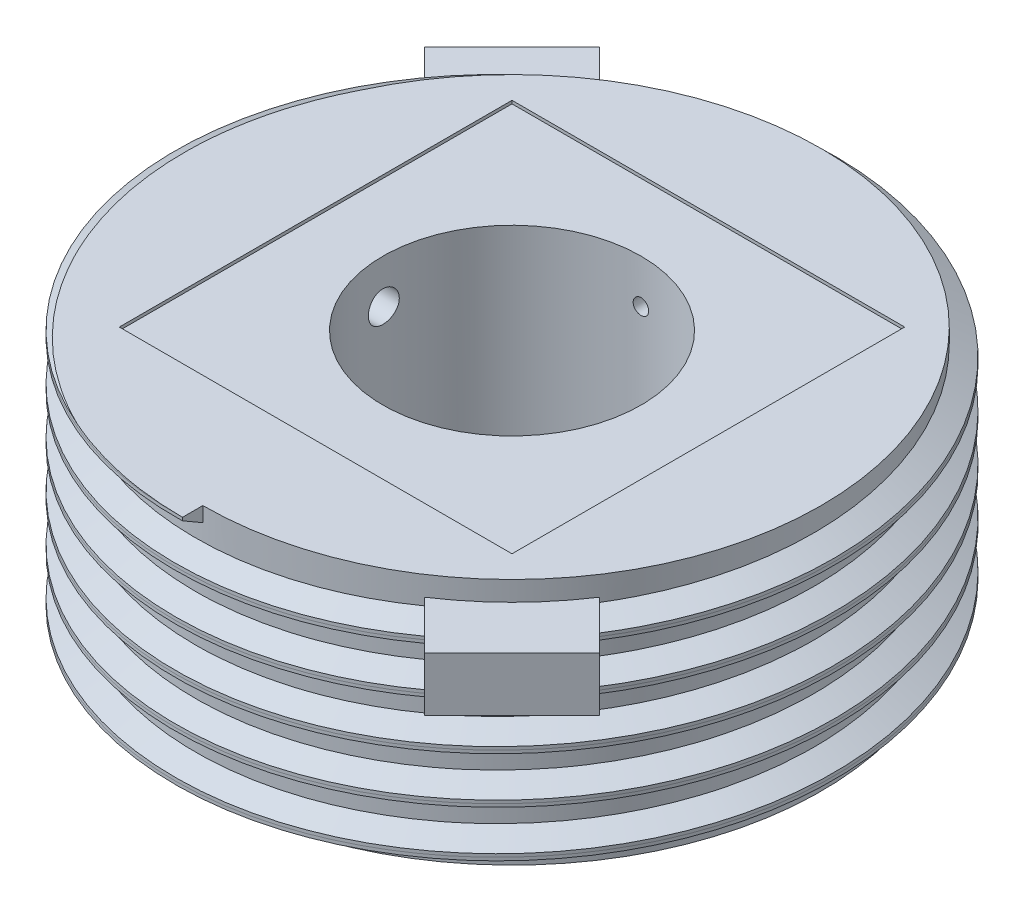
SolidWorks part; units mm, degrees
ref_plane "Front Plane" through (0, 0, 0) normal (0, 0, 1) x (1, 0, 0)
ref_plane "Top Plane" through (0, 0, 0) normal (0, 1, 0) x (1, 0, 0)
ref_plane "Right Plane" through (0, 0, 0) normal (1, 0, 0) x (0, 0, -1)
sketch "innerCircle" plane through (0, 0, 0) normal (0, 1, 0) x (1, 0, 0)
  circle A0 centre (0, 0) radius 7.35
  circle A1 centre (0, 0) radius 20
  dimension "D1" = 14.7
  dimension "D2" = 40
extrude "Circle" add sketch "innerCircle" along normal blind 16
sketch "Sketch5" plane through (0, 16, 0) normal (0, 1, 0) x (1, 0, 0)
  line L1 (12.7, 12.7) -> (-12.7, 12.7)
  line L2 (12.7, 12.7) -> (12.7, -12.7)
  line L3 (12.7, -12.7) -> (-12.7, -12.7)
  line L4 (-12.7, 12.7) -> (-12.7, -12.7)
  line L5 (12.7, 12.7) -> (-12.7, -12.7) construction
  line L6 (12.7, -12.7) -> (-12.7, 12.7) construction
  point P0 (0, 0)
  dimension "D1" = 25.4
  dimension "D2" = 25.4
sketch "Sketch11" plane through (0, 0, 0) normal (0, 0, 1) x (1, 0, 0)
  line L0 (0, 16) -> (0, 0) construction
ref_plane "Plane1" through (0, 16, 0) normal (0, 1, 0) x (1, 0, 0)
sketch "Sketch13" plane through (0, 16, 0) normal (0, 1, 0) x (1, 0, 0)
  circle A0 centre (0, 0) radius 20
curve "Helix/Spiral1" pitch 3 height 16 radius 20 centre (0, 16, 0) axis (0, -1, 0) start towards (0, 0, 1)
sketch "Sketch14" plane through (0, 0, 0) normal (1, 0, 0) x (0, 0, -1)
  line L0 (-19.8126, 16) -> (-21.3126, 16) construction
  line L1 (20, 16) -> (-20, 16) construction
  line L2 (-21.3126, 16) -> (-21.3126, 16.2)
  line L3 (-21.3126, 16.2) -> (-19.8126, 17.066)
  line L4 (-19.8126, 17.066) -> (-19.8126, 14.934)
  line L5 (-19.8126, 14.934) -> (-21.3126, 15.8)
  line L6 (-21.3126, 15.8) -> (-21.3126, 16)
  dimension "D1" = 1.5
  dimension "D2" = 60
  dimension "D3" = 0.2
sweep "Sweep1" add profiles "Sketch14" path "Helix/Spiral1"
sketch "Sketch15" plane through (0, 0, 0) normal (1, 0, 0) x (0, 0, -1)
  line L0 (0, 16) -> (0, 0) construction
  circle A0 centre (0, 12.9718) radius 1
  dimension "D1" = 2
sketch "Sketch16" plane through (0, 0, 0) normal (0, 0, 1) x (1, 0, 0)
  line L0 (0, 11.9718) -> (0, 13.9718) construction
  circle A0 centre (0, 12.9718) radius 0.5
  dimension "D1" = 1
extrude "Cut-Extrude2" cut sketch "Sketch16" against normal through all
extrude "Cut-Extrude3" cut sketch "Sketch15" against normal through all
ref_plane "Plane2" through (0, 0, 0) normal (0.7071, 0, 0.7071) x (0, -1, 0)
sketch "Sketch17" plane through (0, 0, 0) normal (0.7071, 0, 0.7071) x (0, -1, 0)
  line L1 (-11.2218, -4) -> (-14.7218, -4)
  line L2 (-11.2218, -4) -> (-11.2218, 4)
  line L3 (-11.2218, 4) -> (-14.7218, 4)
  line L4 (-14.7218, -4) -> (-14.7218, 4)
  line L5 (-11.2218, -4) -> (-14.7218, 4) construction
  line L6 (-11.2218, 4) -> (-14.7218, -4) construction
  point P0 (-12.9718, 0)
  dimension "D1" = 8
  dimension "D2" = 3.5
extrude "Boss-Extrude1" add sketch "Sketch17" along normal blind 24 and the other way blind 24
sketch "Sketch18" plane through (0, 0, 0) normal (0, 1, 0) x (1, 0, 0)
  circle A0 centre (0, 0) radius 8.35
  dimension "D1" = 16.7
extrude "Cut-Extrude4" cut sketch "Sketch18" along normal through all
sketch "Sketch19" plane through (0, 0, 0) normal (1, 0, 0) x (0, 0, -1)
  line L0 (25, -2) -> (-25, -2) construction
  line L1 (-19.9189, 0) -> (20.6045, 0)
  line L2 (-19.9189, 0) -> (-19.9189, -2)
  line L3 (-19.9189, -2) -> (20.6045, -2)
  line L4 (20.6045, 0) -> (20.6045, -2)
  spline S0 degree 2 poles (-16.6848, 12.3216) (-20, 12.1809) (-20, 12.0422) (-20, 11.8922) (-16.1803, 11.7422) (-12.3607, 11.5922) (-6.1803, 11.4422) (0, 11.2922) (6.1803, 11.1422) (12.3607, 10.9922) (16.1803, 10.8422) (20, 10.6922) (20, 10.5422) (20, 10.3922) (16.1803, 10.2422) (12.3607, 10.0922) (6.1803, 9.9422) (0, 9.7922) (-6.1803, 9.6422) (-12.3607, 9.4922) (-16.1803, 9.3422) (-20, 9.1922) (-20, 9.0422) (-20, 8.8922) (-16.1803, 8.7422) (-12.3607, 8.5922) (-6.1803, 8.4422) (0, 8.2922) (6.1803, 8.1422) (12.3607, 7.9922) (16.1803, 7.8422) (20, 7.6922) (20, 7.5422) (20, 7.3922) (16.1803, 7.2422) (12.3607, 7.0922) (6.1803, 6.9422) (0, 6.7922) (-6.1803, 6.6422) (-12.3607, 6.4922) (-16.1803, 6.3422) (-20, 6.1922) (-20, 6.0422) (-20, 5.8922) (-16.1803, 5.7422) (-12.3607, 5.5922) (-6.1803, 5.4422) (0, 5.2922) (6.1803, 5.1422) (12.3607, 4.9922) (16.1803, 4.8422) (20, 4.6922) (20, 4.5422) (20, 4.3922) (16.1803, 4.2422) (12.3607, 4.0922) (6.1803, 3.9422) (0, 3.7922) (-6.1803, 3.6422) (-12.3607, 3.4922) (-16.1803, 3.3422) (-20, 3.1922) (-20, 3.0422) (-20, 2.8922) (-16.1803, 2.7422) (-12.3607, 2.5922) (-6.1803, 2.4422) (0, 2.2922) (6.1803, 2.1422) (12.3607, 1.9922) (16.1803, 1.8422) (20, 1.6922) (20, 1.5422) (20, 1.3922) (16.1803, 1.2422) (12.3607, 1.0922) (6.1803, 0.9422) (0, 0.7922) (-6.1803, 0.6422) (-12.3607, 0.4922) (-16.1803, 0.3422) (-20, 0.1922) (-20, 0.0422) (-20, 0.0213) (-19.9189, 0) knots 0.15119 0.15119 0.15119 0.166667 0.166667 0.183333 0.183333 0.2 0.2 0.216667 0.216667 0.233333 0.233333 0.25 0.25 0.266667 0.266667 0.283333 0.283333 0.3 0.3 0.316667 0.316667 0.333333 0.333333 0.35 0.35 0.366667 0.366667 0.383333 0.383333 0.4 0.4 0.416667 0.416667 0.433333 0.433333 0.45 0.45 0.466667 0.466667 0.483333 0.483333 0.5 0.5 0.516667 0.516667 0.533333 0.533333 0.55 0.55 0.566667 0.566667 0.583333 0.583333 0.6 0.6 0.616667 0.616667 0.633333 0.633333 0.65 0.65 0.666667 0.666667 0.683333 0.683333 0.7 0.7 0.716667 0.716667 0.733333 0.733333 0.75 0.75 0.766667 0.766667 0.783333 0.783333 0.8 0.8 0.816667 0.816667 0.833333 0.833333 0.835748 0.835748 0.835748 weights 0.993509 0.954551 1 0.951057 1 0.951057 1 0.951057 1 0.951057 1 0.951057 1 0.951057 1 0.951057 1 0.951057 1 0.951057 1 0.951057 1 0.951057 1 0.951057 1 0.951057 1 0.951057 1 0.951057 1 0.951057 1 0.951057 1 0.951057 1 0.951057 1 0.951057 1 0.951057 1 0.951057 1 0.951057 1 0.951057 1 0.951057 1 0.951057 1 0.951057 1 0.951057 1 0.951057 1 0.951057 1 0.951057 1 0.951057 1 0.951057 1 0.951057 1 0.951057 1 0.951057 1 0.951057 1 0.951057 1 0.951057 1 0.951057 1 0.99291 0.987874 construction
  dimension "D1" = 40.5234
  dimension "D2" = 2
extrude "Cut-Extrude5" cut sketch "Sketch19" against normal through all both and the other way through all
sketch "Sketch20" plane through (0, 0, 0) normal (1, 0, 0) x (0, 0, -1)
  line L1 (20, 16) -> (-21.3126, 16)
  line L2 (20, 16) -> (20, 18.2403)
  line L3 (20, 18.2403) -> (-21.3126, 18.2403)
  line L4 (-21.3126, 16) -> (-21.3126, 18.2403)
  dimension "D1" = 41.3126
  dimension "D2" = 2.2403
extrude "Cut-Extrude6" cut sketch "Sketch20" against normal through all both and the other way through all
sketch "Sketch21" plane through (0, 0, 0) normal (0, -1, 0) x (1, 0, 0)
  circle A0 centre (0, 0) radius 14
  circle A1 centre (0, 0) radius 12.3
  dimension "D1" = 28
  dimension "D2" = 1.7
extrude "Cut-Extrude7" cut sketch "Sketch21" against normal blind 0.7
sketch "Sketch22" plane through (0, 16, 0) normal (0, 1, 0) x (1, 0, 0)
  line L1 (-12.7, -12.7) -> (12.7, -12.7)
  line L2 (-12.7, -12.7) -> (-12.7, 12.7)
  line L3 (-12.7, 12.7) -> (12.7, 12.7)
  line L4 (12.7, -12.7) -> (12.7, 12.7)
  line L5 (-12.7, -12.7) -> (12.7, 12.7) construction
  line L6 (-12.7, 12.7) -> (12.7, -12.7) construction
  point P0 (0, 0)
extrude "Cut-Extrude8" cut sketch "Sketch22" against normal blind 0.2
equation "\"1inch\"=30"
